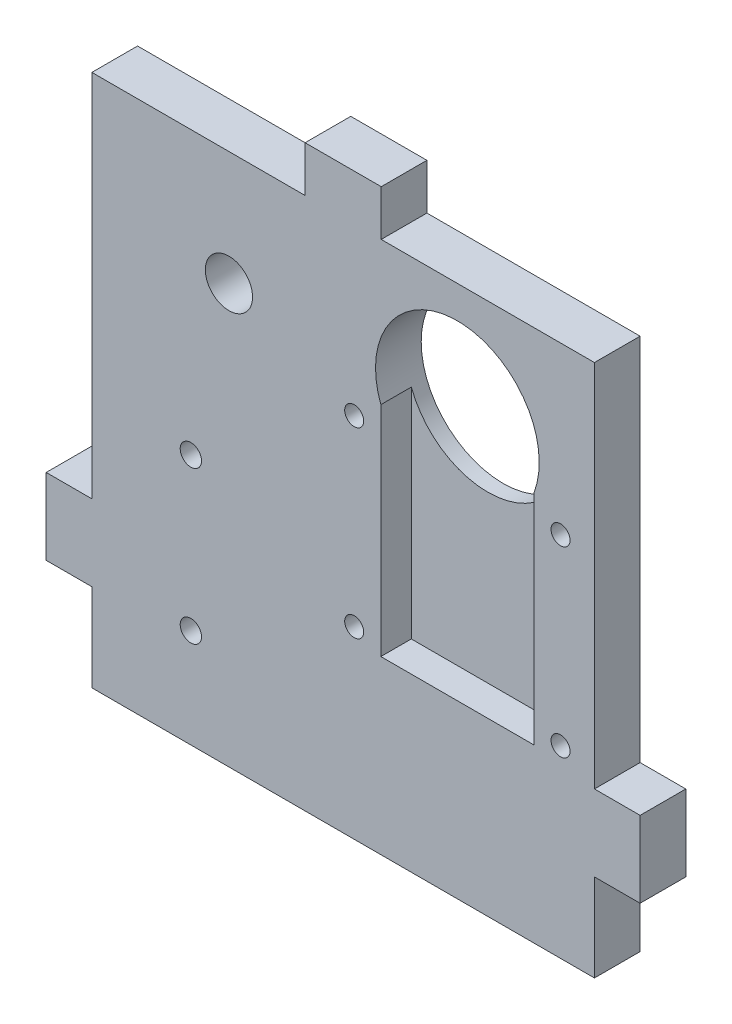
SolidWorks part; units mm, degrees
ref_plane "Plan de face" through (0, 0, 0) normal (0, 0, 1) x (1, 0, 0)
ref_plane "Plan de dessus" through (0, 0, 0) normal (0, 1, 0) x (1, 0, 0)
ref_plane "Plan de droite" through (0, 0, 0) normal (1, 0, 0) x (0, 0, -1)
sketch "Esquisse1" plane through (0, 0, 0) normal (0, 0, 1) x (1, 0, 0)
  line L0 (-15, 0) -> (15, 0)
  line L1 (0, 34.4414) -> (0, -34.4414) construction
  line L2 (33, 15) -> (-33, 15)
  line L3 (-33, 15) -> (-33, -55)
  line L4 (-33, -55) -> (33, -55)
  line L5 (33, 15) -> (33, -55)
  circle A1 centre (15, 0) radius 10.75
  circle A4 centre (-20, -42) radius 1.4
  circle A5 centre (-20, -22) radius 1.4
  circle A6 centre (-15, 0) radius 3.1
  point P3 (0, 0)
  point P14 (0, 15)
  point P15 (-15, 0)
  point P16 (15, 0)
  dimension "D5" = 6.2
  dimension "D7" = 2.8
  dimension "D8" = 2.8
  dimension "D10" = 13
  dimension "D11" = 13
  dimension "D13" = 21.5
  dimension "D1" = 15
  dimension "D2" = 33
  dimension "D3" = 70
  dimension "D4" = 15
  dimension "D6" = 66
  dimension "D9" = 13
  dimension "D12" = 20
extrude "Boss.-Extru.1" add sketch "Esquisse1" along normal blind 6 contours L5 L2 region at (-1.1263, -21.8311, 0)
sketch "Esquisse2" plane through (0, 0, 6) normal (0, 0, 1) x (1, 0, 0)
  line L1 (33, 15) -> (-33, 15) construction
  line L2 (-5, 15) -> (5, 15)
  line L3 (-5, 15) -> (-5, 21)
  line L4 (-5, 21) -> (5, 21)
  line L7 (5, 15) -> (5, 21)
  line L8 (-33, 15) -> (-33, -55) construction
  line L9 (33, 15) -> (33, -55) construction
  line L10 (-33, -33.5) -> (-39, -33.5)
  line L11 (-33, -33.5) -> (-33, -43.5)
  line L12 (-33, -43.5) -> (-39, -43.5)
  line L13 (-39, -33.5) -> (-39, -43.5)
  line L14 (33, -33.5) -> (39, -33.5)
  line L15 (33, -33.5) -> (33, -43.5)
  line L16 (33, -43.5) -> (39, -43.5)
  line L17 (39, -33.5) -> (39, -43.5)
  line L18 (-33, -55) -> (33, -55) construction
  dimension "D1" = 28
  dimension "D2" = 10
  dimension "D3" = 6
  dimension "D4" = 6
  dimension "D5" = 10
  dimension "D6" = 11.5
  dimension "D7" = 11.5
  dimension "D8" = 10
  dimension "D9" = 6
extrude "Boss.-Extru.3" add sketch "Esquisse2" against normal blind 6
sketch "Esquisse3" plane through (0, 0, 6) normal (0, 0, 1) x (1, 0, 0)
  line L0 (4.95, -3.8158) -> (4.95, -32.4658)
  line L1 (4.95, -32.4658) -> (25.05, -32.4658)
  line L2 (25.05, -32.4658) -> (25.05, -3.8158)
  circle A0 centre (15, 0) radius 10.75 construction
  arc A1 (4.95, -3.8158) -> (25.05, -3.8158) centre (15, 0) ccw
  dimension "D1" = 28.65
  dimension "D2" = 20.1
  dimension "D3" = 28.65
extrude "Enlèv. mat.-Extru.3" cut sketch "Esquisse3" against normal blind 4
sketch "Esquisse4" plane through (0, 0, 6) normal (0, 0, 1) x (1, 0, 0)
  line L0 (4.95, -3.8158) -> (4.95, -32.4658) construction
  line L1 (25.05, -32.4658) -> (25.05, -3.8158) construction
  line L3 (4.95, -32.4658) -> (25.05, -32.4658) construction
  circle A0 centre (28.55, -6.8158) radius 1.25
  circle A2 centre (28.55, -30.8158) radius 1.25
  circle A4 centre (1.45, -30.8158) radius 1.25
  circle A6 centre (1.45, -6.8158) radius 1.25
  dimension "D1" = 2.5
  dimension "D2" = 2.5
  dimension "D3" = 2.5
  dimension "D4" = 2.5
  dimension "D5" = 24
  dimension "D6" = 24
  dimension "D7" = 3.5
  dimension "D8" = 3.5
  dimension "D9" = 3.5
  dimension "D10" = 3.5
  dimension "D11" = 1.65
  dimension "D12" = 1.65
extrude "Enlèv. mat.-Extru.4" cut sketch "Esquisse4" against normal blind 6
